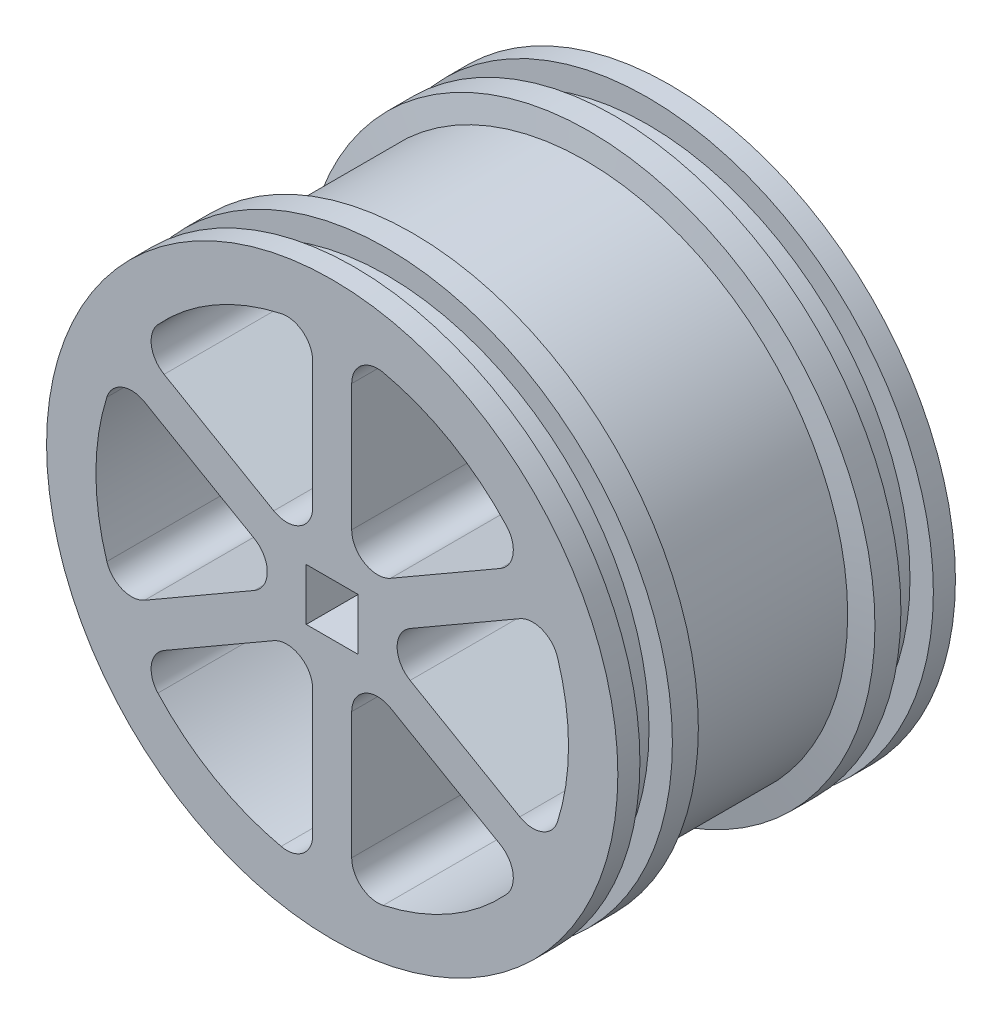
SolidWorks part; units mm, degrees
ref_plane "Front Plane" through (0, 0, 0) normal (0, 0, 1) x (1, 0, 0)
ref_plane "Top Plane" through (0, 0, 0) normal (0, 1, 0) x (1, 0, 0)
ref_plane "Right Plane" through (0, 0, 0) normal (1, 0, 0) x (0, 0, -1)
sketch "Sketch1" plane through (0, 0, 0) normal (1, 0, 0) x (0, 0, -1)
  line L1 (0, 22) -> (1.7, 22)
  line L2 (1.7, 22) -> (1.7, 20.2)
  line L3 (1.7, 20.2) -> (4.2, 20.2)
  line L4 (4.2, 20.2) -> (4.2, 22)
  line L5 (4.2, 22) -> (6.2, 22)
  line L6 (6.2, 22) -> (6.5, 20.2)
  line L7 (19.8, 22) -> (19.5, 20.2)
  line L8 (19.5, 20.2) -> (6.5, 20.2)
  line L10 (0, 18.2) -> (26, 18.2)
  line L11 (19.8, 22) -> (21.8, 22)
  line L12 (21.8, 22) -> (21.8, 20.2)
  line L13 (21.8, 20.2) -> (24.3, 20.2)
  line L14 (24.3, 20.2) -> (24.3, 22)
  line L15 (24.3, 22) -> (26, 22)
  line L18 (-0.3222, 0) -> (27.2819, 0) construction
  line L19 (0, 0) -> (0, 18.2) construction
  line L20 (0, 22) -> (0, 1028.7814) construction
  line L21 (0, 22) -> (0, 18.2)
  line L22 (26, 22) -> (26, 18.2)
  dimension "D1" = 22
  dimension "D2" = 1.7
  dimension "D3" = 2
  dimension "D4" = 0.3
  dimension "D5" = 2.3
  dimension "D6" = 3.8
  dimension "D7" = 1.8
  dimension "D8" = 2.5
  dimension "D9" = 26
revolve "Revolve1" add sketch "Sketch1" angle 360 about L18
sketch "Sketch2" plane through (0, 0, 0) normal (0, 0, 1) x (1, 0, 0)
  line L0 (0, 0) -> (0, 18.2) construction
  line L1 (-1.5, 18.2) -> (-1.5, 0)
  line L2 (-1.5, 18.2) -> (1.5, 18.2)
  line L3 (-1.5, 0) -> (1.5, 0)
  line L4 (1.5, 18.2) -> (1.5, 0)
  line L5 (-1.5, 18.2) -> (1.5, 0) construction
  line L6 (-1.5, 0) -> (1.5, 18.2) construction
  circle A0 centre (0, 0) radius 18.2 construction
  point P6 (0, 9.1)
  dimension "D1" = 18.2
  dimension "D2" = 3
extrude "Boss-Extrude1" add sketch "Sketch2" against normal blind 24
pattern_circular "CirPattern1" count 6 over 360 about axis through (0, 0, 0.3222) along (0, 0, 1) of "Boss-Extrude1" reverse direction yes
sketch "Sketch3" plane through (0, 0, 0) normal (0, 0, 1) x (1, 0, 0)
  line L1 (-2, -2) -> (2, -2)
  line L2 (-2, -2) -> (-2, 2)
  line L3 (-2, 2) -> (2, 2)
  line L4 (2, -2) -> (2, 2)
  line L5 (-2, -2) -> (2, 2) construction
  line L6 (-2, 2) -> (2, -2) construction
  point P0 (0, 0)
  dimension "D1" = 4
extrude "Cut-Extrude1" cut sketch "Sketch3" against normal through all both and the other way through all
fillet "Fillet1" radius 2 18 edges at (-14.958, 10.3681, -12) (16.458, -7.77, -12) (-1.5, 18.1381, -12) (-1.5, 2.5981, -12) (1.5, 18.1381, -12) (14.958, 10.3681, -12) (1.5, 2.5981, -12) (16.458, 7.77, -12) (3, 0, -12) (1.5, -2.5981, -12) (14.958, -10.3681, -12) (1.5, -18.1381, -12) (-1.5, -2.5981, -12) (-1.5, -18.1381, -12) (-14.958, -10.3681, -12) (-16.458, -7.77, -12) (-16.458, 7.77, -12) (-3, 0, -12)
fillet "Fillet2" radius 2 1 edges at (18.2, 0, -26)
